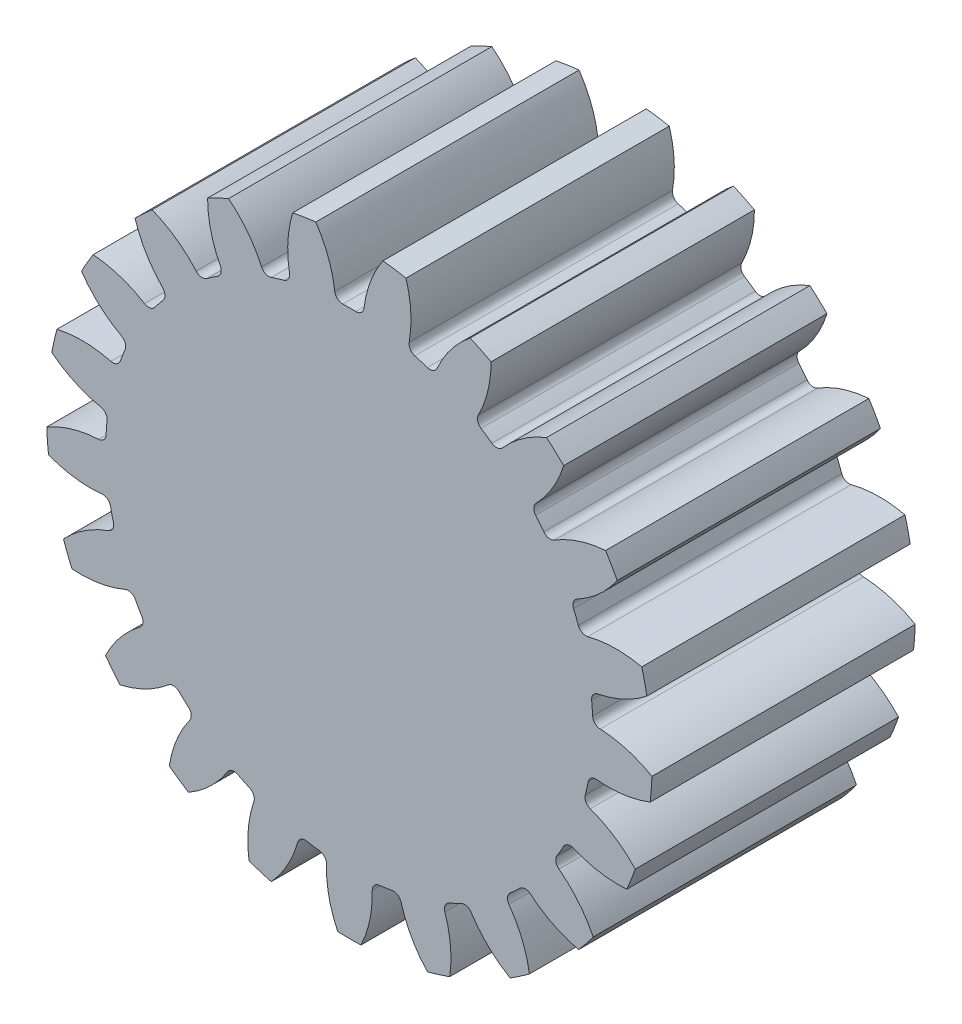
SolidWorks part; units mm, degrees
ref_plane "Front Plane" through (0, 0, 0) normal (0, 0, 1) x (1, 0, 0)
ref_plane "Top Plane" through (0, 0, 0) normal (0, 1, 0) x (1, 0, 0)
ref_plane "Right Plane" through (0, 0, 0) normal (1, 0, 0) x (0, 0, -1)
sketch "Sketch2" plane through (0, 0, 0) normal (0, 0, 1) x (1, 0, 0)
  circle A0 centre (0, 0) radius 21 construction
  circle A1 centre (0, 0) radius 23
  dimension "D1" = 42
  dimension "D2" = 46
extrude "Boss-Extrude1" add sketch "Sketch2" along normal mid plane 20 contours A1
sketch "Sketch3" plane through (0, 0, 0) normal (0, 0, 1) x (1, 0, 0)
  line L0 (0, 23) -> (0, 0) construction
  line L1 (0, 0) -> (6.7794, 21.9782) construction
  line L2 (0, 0) -> (3.428, 22.7431) construction
  line L3 (-1.0601, 18.4696) -> (0, 0) construction
  line L4 (-1.5693, 20.9413) -> (1.5693, 20.9413) construction
  line L5 (1.5693, 20.9413) -> (4.6729, 20.4735) construction
  line L6 (-2.2775, 22.887) -> (0, 16.6296) construction
  circle A0 centre (0, 0) radius 19 construction
  arc A1 (1.0601, 18.4696) -> (-1.0601, 18.4696) centre (0, 0) ccw
  circle A2 centre (0, 0) radius 23 construction
  circle A3 centre (0, 0) radius 21 construction
  arc A4 (-2.5513, 22.8581) -> (-1.0601, 18.4696) centre (-9.7269, 17.9722) cw
  arc A5 (2.5513, 22.8581) -> (1.0601, 18.4696) centre (9.7269, 17.9722) ccw
  arc A6 (2.5513, 22.8581) -> (-2.5513, 22.8581) centre (0, 0) ccw
  dimension "D4" = 42
  dimension "D1" = 17.143
  dimension "D2" = 4
  dimension "D3" = 4.5
  dimension "D5" = 20
extrude "Cut-Extrude1" cut sketch "Sketch3" against normal through all both and the other way through all
fillet "Fillet1" radius 0.6 2 edges at (1.0601, 18.4696, 0) (-1.0601, 18.4696, 0)
ref_axis "Axis1" through (0, 0, -11) along (0, 0, 1)
pattern_circular "CirPattern1" count 21 over 360 about axis through (0, 0, -11) along (0, 0, 1) of "Cut-Extrude1", "Fillet1"
sketch "Sketch4" plane through (0, 0, -10) normal (0, 0, -1) x (-1, 0, 0)
  line L0 (-1.5, 2) -> (1.5, 2)
  arc A0 (-1.5, 2) -> (1.5, 2) centre (0, 0) ccw
  dimension "D1" = 5
  dimension "D2" = 2
extrude "Cut-Extrude3" cut sketch "Sketch4" against normal blind 10
equation "\"Module\"= 2"
equation "\"Number of teeth\"= 21"
equation "\"pressure angle\"= 20"
equation "\"D1@Sketch2\"=\"Module\"*\"Number of teeth\""
equation "\"D2@Sketch2\"=(\"Number of teeth\"+2) *\"Module\""
equation "\"D1@Sketch3\"=360 /\"Number of teeth\""
equation "\"D2@Sketch3\"=\"Module\"*2"
equation "\"D3@Sketch3\"=\"Module\" *if( \"Module\"=> 1.25,2.25,2.4)"
equation "\"D5@Sketch3\"=\"pressure angle\""
equation "\"D4@Sketch3\"=\"Module\"*\"Number of teeth\""
equation "\"D1@CirPattern1\"=\"Number of teeth\""
equation "\"D1@Fillet1\"=0.3 *\"Module\""
